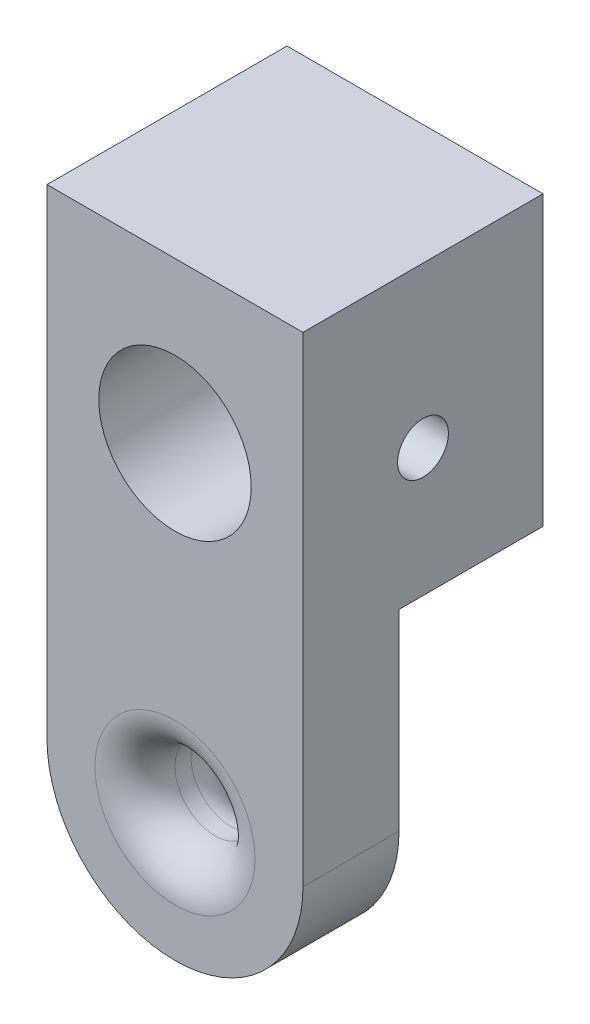
SolidWorks part; units mm, degrees
material "Delrin 2700 NC010, Low Viscosity Acetal Copolymer (SS)"
ref_plane "Front" through (0, 0, 0) normal (0, 0, 1) x (1, 0, 0)
ref_plane "Top" through (0, 0, 0) normal (0, 1, 0) x (1, 0, 0)
ref_plane "Right" through (0, 0, 0) normal (1, 0, 0) x (0, 0, -1)
sketch "Sketch1" plane through (0, 0, 0) normal (0, 0, 1) x (1, 0, 0)
  line L0 (0, 20) -> (0, 0) construction
  line L1 (-8, 12) -> (-8, 0)
  line L2 (8, 12) -> (8, 0)
  line L5 (8, 12) -> (8, 30)
  line L6 (8, 30) -> (-8, 30)
  line L7 (-8, 30) -> (-8, 12)
  line L9 (-5, 26.35) -> (5, 26.35) construction
  line L10 (-5, 26.35) -> (-5, 13.65) construction
  line L11 (-5, 13.65) -> (5, 13.65) construction
  line L12 (5, 26.35) -> (5, 13.65) construction
  line L13 (-5, 26.35) -> (5, 13.65) construction
  line L14 (-5, 13.65) -> (5, 26.35) construction
  arc A0 (-8, 0) -> (8, 0) centre (0, 0) ccw
  circle A2 centre (0, 0) radius 2.5
  circle A3 centre (0, 20) radius 2.6 construction
  dimension "D1" = 16
  dimension "D2" = 16
  dimension "D4" = 5.2
  dimension "D5" = 5
  dimension "D3" = 20
  dimension "D6" = 10
  dimension "D7" = 18
  dimension "D8" = 10
  dimension "D9" = 12.7
extrude "Boss-Extrude1" add sketch "Sketch1" along normal blind 15
sketch "Sketch6" plane through (0, 0, 0) normal (0, 0, 1) x (1, 0, 0)
  line L0 (8, 0) -> (8, 30) construction
  line L1 (8, 12) -> (-8, 12)
  line L2 (8, 12) -> (8, -8)
  line L3 (8, -8) -> (-8, -8)
  line L4 (-8, 12) -> (-8, -8)
  line L5 (-8, 30) -> (-8, 0) construction
  arc A0 (-8, 0) -> (8, 0) centre (0, 0) ccw construction
  dimension "D1" = 20
extrude "Cut-Extrude1" cut sketch "Sketch6" along normal blind 9
fillet "Fillet1" radius 2.5 2 edges at (2.5, 0, 15) (-2.5, 0, 9)
hole_wizard "3/8 (0.3750) Dowel Hole1" positions "Sketch2" profile "Sketch3" hole size "3/8" standard "ANSI Inch" end condition through all
sketch "Sketch2" plane through (0, 0, 15) normal (0, 0, 1) x (1, 0, 0)
  point P0 (0, 20)
sketch "Sketch3" plane through (0, 20, 15) normal (1, 0, 0) x (0, -1, 0)
  line L0 (0, 0) -> (0, 15)
  line L1 (0, 15) -> (4.7625, 15)
  line L2 (4.7625, 15) -> (4.7625, 0)
  line L5 (4.7625, 0) -> (0, 0)
  line L11 (0, -6.35) -> (0, 107.95) construction
  dimension "Thru Hole Dia." = 9.525
  dimension "Thru Hole Depth" = 15
hole_wizard "1/8 (0.1250) Dowel Hole1" positions "Sketch4" profile "Sketch5" hole size "1/8" standard "ANSI Inch" end condition through all
sketch "Sketch4" plane through (-8, 0, 0) normal (-1, 0, 0) x (0, 0, 1)
  line L0 (7.5, 30) -> (7.5, 20) construction
  line L1 (15, 30) -> (0, 30) construction
  point P0 (7.5, 20)
sketch "Sketch5" plane through (-8, 20, 7.5) normal (0, 1, 0) x (0, 0, 1)
  line L0 (0, 0) -> (0, 16)
  line L1 (0, 16) -> (1.5875, 16)
  line L2 (1.5875, 16) -> (1.5875, 0)
  line L5 (1.5875, 0) -> (0, 0)
  line L11 (0, -6.35) -> (0, 107.95) construction
  dimension "Thru Hole Dia." = 3.175
  dimension "Thru Hole Depth" = 16
